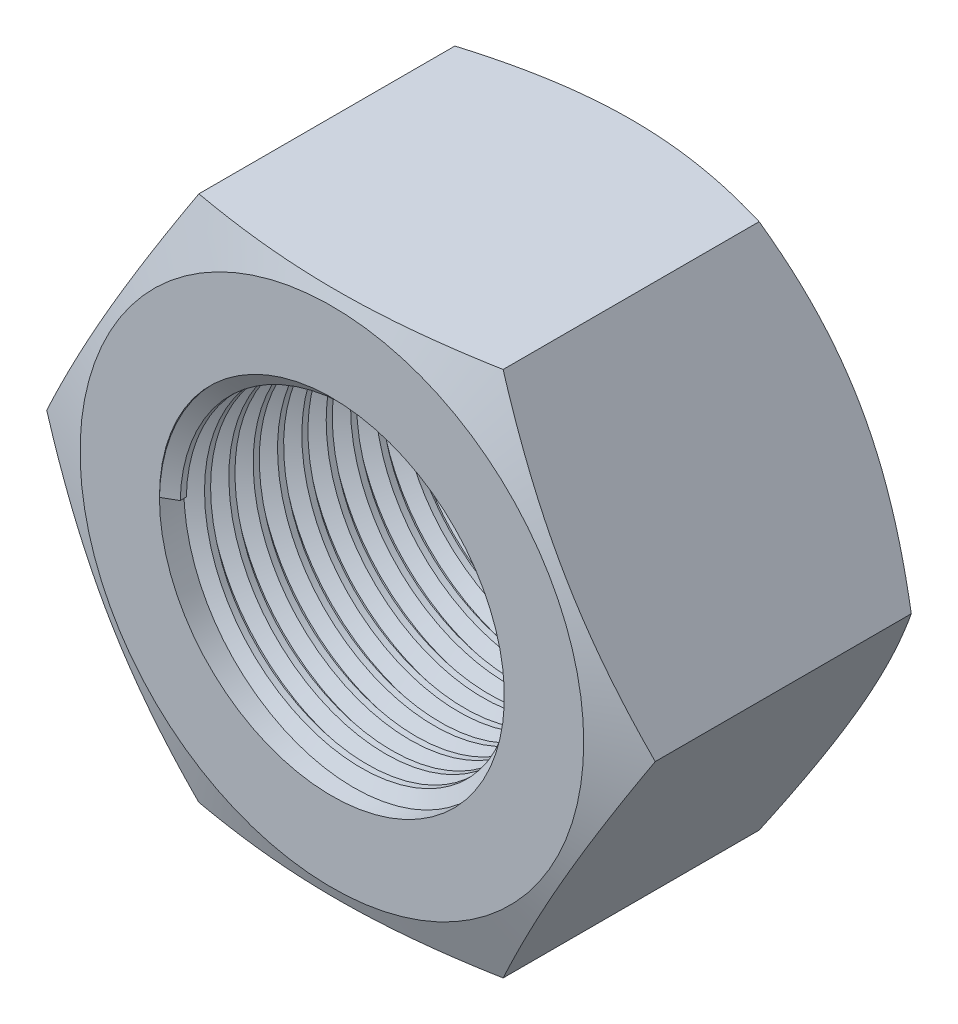
SolidWorks part; units mm, degrees
ref_plane "Alzado" through (0, 0, 0) normal (0, 0, 1) x (1, 0, 0)
ref_plane "Planta" through (0, 0, 0) normal (0, 1, 0) x (1, 0, 0)
ref_plane "Vista lateral" through (0, 0, 0) normal (1, 0, 0) x (0, 0, -1)
sketch "Croquis1" plane through (0, 0, 0) normal (0, 0, 1) x (1, 0, 0)
  line L1 (15.8771, 0) -> (7.9386, 13.75)
  line L2 (7.9386, 13.75) -> (-7.9386, 13.75)
  line L3 (-7.9386, 13.75) -> (-15.8771, 0)
  line L4 (-15.8771, 0) -> (-7.9386, -13.75)
  line L5 (-7.9386, -13.75) -> (7.9386, -13.75)
  line L6 (7.9386, -13.75) -> (15.8771, 0)
  circle A0 centre (0, 0) radius 9
  circle A1 centre (0, 0) radius 13.75 construction
  dimension "D1" = 18
  dimension "D2" = 27.5
extrude "Saliente-Extruir1" add sketch "Croquis1" along normal blind 16
thread "Rosca1" pitch 1.27 method extrude profile "Perfil de rosca1" start angle 0, offset 0, length 15, pitch 1.27, diameter 18
ref_plane "Plano1" through (-9, 0, 16) normal (0, -1, 0) x (-1, 0, 0)
sketch "Perfil de rosca1" plane through (-9, 0, 16) normal (0, -1, 0) x (-1, 0, 0)
  line L0 (0, 0) -> (0, 1.27) construction
  line L11 (0, 0) -> (0, 1.1112)
  line L12 (0, 1.1112) -> (-0.6874, 0.7144)
  line L13 (-0.6874, 0.7144) -> (-0.6874, 0.3969)
  line L15 (-0.6874, 0.3969) -> (0, 0)
  line L17 (-0.6874, 0.5556) -> (0, 0.5556) construction
  point P2 (0, 0)
  dimension "Pitch" = 1.27
  dimension "Profile_Angle" = 60
  dimension "Profile_Land" = 0.3175
  dimension "Profile_Height" = 0.6874
sketch "Croquis4" plane through (0, 0, 16) normal (0, 0, 1) x (1, 0, 0)
  circle A0 centre (0, 0) radius 13.1408
  circle A1 centre (0, 0) radius 50
  dimension "D1" = 100
extrude "Cortar-Extruir1" cut sketch "Croquis4" against normal blind 8 draft 70
sketch "Croquis5" plane through (0, 0, 0) normal (0, 0, -1) x (-1, 0, 0)
  circle A0 centre (0, 0) radius 13.1408
  circle A1 centre (0, 0) radius 70.4477
extrude "Cortar-Extruir2" cut sketch "Croquis5" against normal blind 16 draft 59
